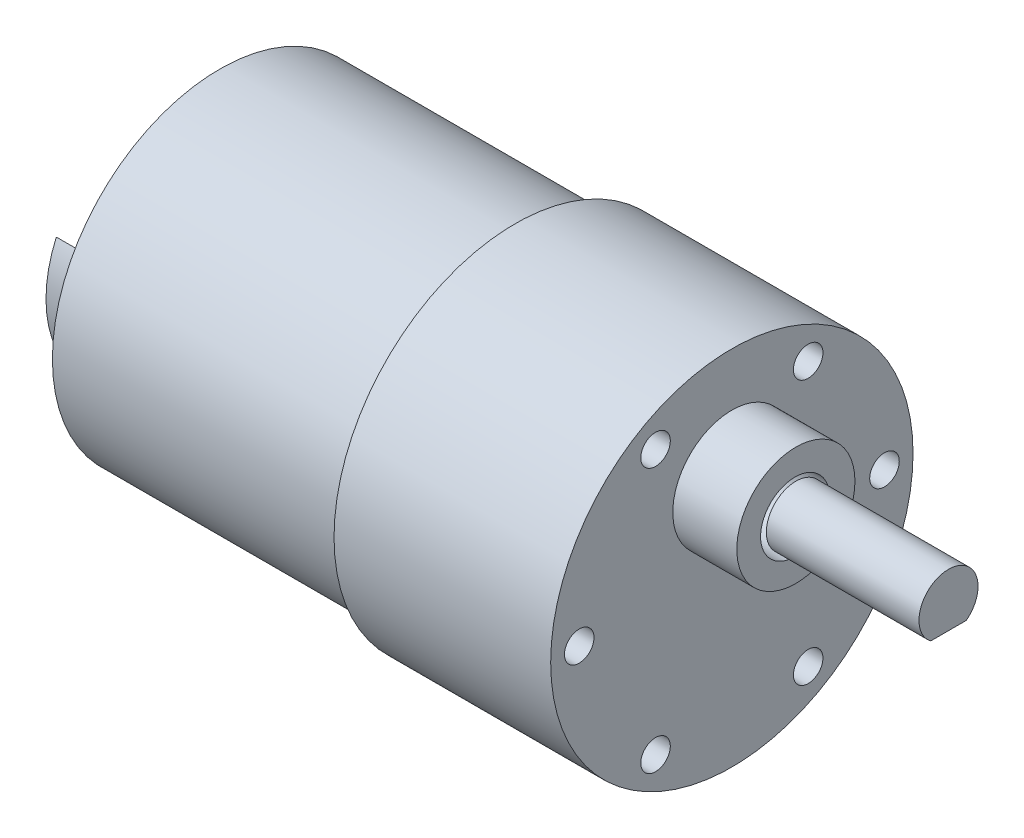
SolidWorks part; units mm, degrees
ref_plane "Plan de face" through (0, 0, 0) normal (0, 0, 1) x (1, 0, 0)
ref_plane "Plan de dessus" through (0, 0, 0) normal (0, 1, 0) x (1, 0, 0)
ref_plane "Plan de droite" through (0, 0, 0) normal (1, 0, 0) x (0, 0, -1)
sketch "Esquisse1" plane through (0, 0, 0) normal (0, 0, 1) x (1, 0, 0)
  line L0 (-22, 18.4) -> (-22, 0)
  line L1 (-22, 0) -> (0, 0)
  line L2 (0, 0) -> (0, 18.4)
  line L3 (0, 18.4) -> (-22, 18.4)
  line L4 (-22, 0) -> (0, 0) construction
revolve "Révolution1" add sketch "Esquisse1" angle 360 about L4 reverse direction yes
sketch "Esquisse2" plane through (-22, 0, 0) normal (-1, 0, 0) x (0, 0, 1)
  circle A0 centre (0, 0) radius 17
extrude "Boss.-Extru.1" add sketch "Esquisse2" along normal blind 30
sketch "Esquisse3" plane through (-52, 0, 0) normal (-1, 0, 0) x (0, 0, 1)
  circle A0 centre (0, 0) radius 12.05
extrude "Boss.-Extru.2" add sketch "Esquisse3" along normal blind 5.6
sketch "Esquisse4" plane through (-57.6, 0, 0) normal (-1, 0, 0) x (0, 0, 1)
  line L0 (11, -4.9196) -> (11, 4.9196)
  arc A0 (11, 4.9196) -> (11, -4.9196) centre (0, 0) ccw
extrude "Enlèv. mat.-Extru.1" cut sketch "Esquisse4" against normal blind 4.6
sketch "Esquisse5" plane through (-53, 0, 0) normal (-1, 0, 0) x (0, 0, 1)
  line L0 (-11, 4.9196) -> (-11, -4.9196)
  arc A0 (-11, -4.9196) -> (-11, 4.9196) centre (0, 0) cw
extrude "Boss.-Extru.3" add sketch "Esquisse5" along normal blind 4.6
sketch "Esquisse6" plane through (0, 0, 0) normal (1, 0, 0) x (0, 0, -1)
  circle A0 centre (0, 7) radius 6
extrude "Boss.-Extru.4" add sketch "Esquisse6" along normal blind 6.5
sketch "Esquisse7" plane through (6.5, 0, 0) normal (1, 0, 0) x (0, 0, -1)
  circle A0 centre (0, 7) radius 3
extrude "Boss.-Extru.5" add sketch "Esquisse7" along normal blind 15.5
sketch "Esquisse8" plane through (22, 0, 0) normal (1, 0, 0) x (0, 0, -1)
  line L0 (1.8, 4.6) -> (-1.8, 4.6)
  arc A0 (-1.8, 4.6) -> (1.8, 4.6) centre (0, 7) ccw
extrude "Enlèv. mat.-Extru.2" cut sketch "Esquisse8" against normal blind 12
hole_wizard "Diamètre du perçage Ø3.0 (3)1" positions "Esquisse10" profile "Esquisse9" hole size "Ø3.0" standard "Ansi Metric"
sketch "Esquisse10" plane through (0, 0, 0) normal (1, 0, 0) x (0, 0, -1)
  point P0 (15.5, 0)
  point P1 (-7.75, -13.4234)
  point P2 (-7.75, 13.4234)
  point P3 (7.75, -13.4234)
  point P4 (7.75, 13.4234)
  point P5 (-15.5, 0)
sketch "Esquisse9" plane through (0, 0, -15.5) normal (0, 1, 0) x (0, 0, -1)
  line L0 (0, 0) -> (0, 4)
  line L1 (0, 4) -> (1.5, 4)
  line L2 (1.5, 4) -> (1.5, 0)
  line L5 (1.5, 0) -> (0, 0)
  line L10 (0, 4) -> (-1.5, 4) construction
  line L11 (0, -6.35) -> (0, 107.95) construction
  dimension "Diamètre du perçage" = 3
  dimension "Profondeur du perçage" = 4
  dimension "Angle de pointe" = 180
ref_axis "Axe1" through (22.3696, 7, 0) along (-1, 0, 0)
ref_axis "Axe2" through (-53.0409, 7, 0) along (-1, 0, 0)
sketch "Esquisse12" plane through (22, 0, 0) normal (1, 0, 0) x (0, 0, -1)
  circle A0 centre (-0.0865, 6.9091) radius 3.5
  point P2 (0, 0)
  point P3 (1.6896, 9.544)
extrude "Enlèv. mat.-Extru.3" cut sketch "Esquisse12" against normal blind 15 from surface starting at face at (6.5, 7, -6)
